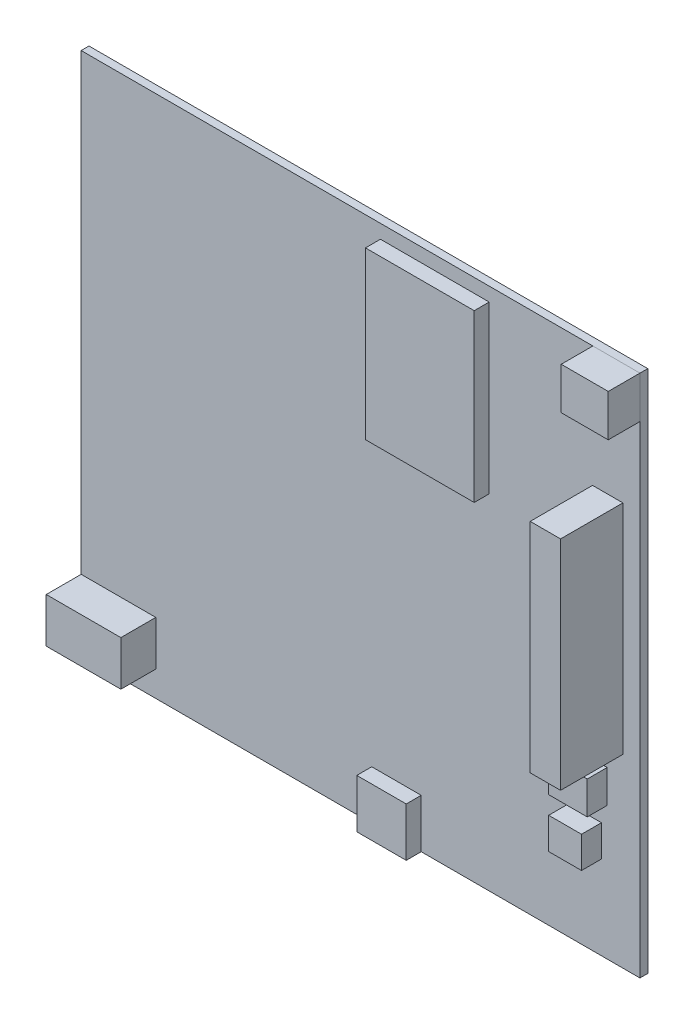
SolidWorks part; units mm, degrees
other "Foot3"
other "Foot2"
other "Foot1"
other "XBee"
other "ResetButton"
other "CommissionButton"
other "GPIO pins"
other "Barrel Jack"
other "mini-usb"
other "SMA connector"
other "base of Board"
other "Foot4"
ref_plane "Front Plane" through (0, 0, 0) normal (0, 0, 1) x (1, 0, 0)
ref_plane "Top Plane" through (0, 0, 0) normal (0, 1, 0) x (1, 0, 0)
ref_plane "Right Plane" through (0, 0, 0) normal (1, 0, 0) x (0, 0, -1)
sketch "Sketch1" plane through (0, 0, 0) normal (0, 0, 1) x (1, 0, 0)
  line L5 (0, 0) -> (112, 0)
  line L6 (0, 0) -> (0, 105)
  line L7 (0, 105) -> (112, 105)
  line L8 (112, 0) -> (112, 105)
  line L9 (59.9873, 68.9382) -> (81.7856, 68.9382)
  line L10 (59.9873, 68.9382) -> (59.9873, 102.2345)
  line L11 (59.9873, 102.2345) -> (81.7856, 102.2345)
  line L12 (81.7856, 68.9382) -> (81.7856, 102.2345)
  line L13 (14.9582, 14.0734) -> (0, 14.0734)
  line L14 (14.9582, 14.0734) -> (14.9582, 5.105)
  line L15 (14.9582, 5.105) -> (0, 5.105)
  line L16 (0, 14.0734) -> (0, 5.105)
  line L17 (97.7092, 33.2654) -> (105.4393, 33.2654)
  line L18 (97.7092, 33.2654) -> (97.7092, 26.6805)
  line L19 (97.7092, 26.6805) -> (105.4393, 26.6805)
  line L20 (105.4393, 33.2654) -> (105.4393, 26.6805)
  line L21 (97.7092, 23.1017) -> (104.2941, 23.1017)
  line L22 (97.7092, 23.1017) -> (97.7092, 16.8031)
  line L23 (97.7092, 16.8031) -> (104.2941, 16.8031)
  line L24 (104.2941, 23.1017) -> (104.2941, 16.8031)
  line L25 (94.5599, 34.4106) -> (108.5886, 34.4106)
  line L26 (94.5599, 34.4106) -> (94.5599, 14.0734)
  line L27 (94.5599, 14.0734) -> (108.5886, 14.0734)
  line L28 (108.5886, 34.4106) -> (108.5886, 14.0734)
  line L29 (58.247, 9.7929) -> (68.1586, 9.7929)
  line L30 (58.247, 9.7929) -> (58.247, 0)
  line L31 (58.247, 0) -> (68.1586, 0)
  line L32 (68.1586, 9.7929) -> (68.1586, 0)
  line L33 (108.5886, 80.7675) -> (102.5068, 80.7675)
  line L34 (108.5886, 80.7675) -> (108.5886, 37.1166)
  line L35 (108.5886, 37.1166) -> (102.5068, 37.1166)
  line L36 (102.5068, 80.7675) -> (102.5068, 37.1166)
  line L37 (102.5742, 96.5922) -> (112, 96.5922)
  line L38 (102.5742, 96.5922) -> (102.5742, 105)
  line L39 (102.5742, 105) -> (112, 105)
  line L40 (112, 96.5922) -> (112, 105)
  point P0 (0, 0)
  dimension "D1" = 105
  dimension "D2" = 112
extrude "Base PCB" add sketch "Sketch1" along normal blind 1.57 contours L37 L38 L7 L6 L13 L14 L15 L5 L30 L29 L32 L8 L36 L33 L34 L35 L12 L9 L10 L11 L25 L28 L27 L26 | L6 L5 L8 L7 region at (52.5383, 51.4076, 0)
extrude "SMA Connector" add sketch "Sketch1<3>" along normal blind 6.35 from surface separate body contours L39 L38 L37 L40 starting at face at (56, 52.5, 1.57)
sketch "Sketch1<3>" plane through (0, 0, 0) normal (0, 0, 1) x (1, 0, 0) same geometry as "Sketch1"
extrude "Mini USB" add sketch "Sketch1<4>" along normal blind 3 from surface separate body contours L29 L32 L31 L30 starting at face at (56, 52.5, 1.57)
sketch "Sketch1<4>" plane through (0, 0, 0) normal (0, 0, 1) x (1, 0, 0) same geometry as "Sketch1"
extrude "Barrel Jack" add sketch "Sketch1<5>" along normal blind 7 from surface separate body contours L13 L16 L15 L14 starting at face at (56, 52.5, 1.57)
sketch "Sketch1<5>" plane through (0, 0, 0) normal (0, 0, 1) x (1, 0, 0) same geometry as "Sketch1"
extrude "GPIO" add sketch "Sketch1<6>" along normal blind 12.5 from surface separate body contours L33 L36 L35 L34 starting at face at (56, 52.5, 1.57)
sketch "Sketch1<6>" plane through (0, 0, 0) normal (0, 0, 1) x (1, 0, 0) same geometry as "Sketch1"
extrude "Buttons" add sketch "Sketch1<7>" along normal blind 4 from surface separate body contours L20 L19 L18 L17 | L24 L23 L22 L21 starting at face at (56, 52.5, 1.57)
sketch "Sketch1<7>" plane through (0, 0, 0) normal (0, 0, 1) x (1, 0, 0) same geometry as "Sketch1"
extrude "Xbee" add sketch "Sketch1<8>" along normal blind 3 from surface separate body contours L9 L12 L11 L10 starting at face at (56, 52.5, 1.57)
sketch "Sketch1<8>" plane through (0, 0, 0) normal (0, 0, 1) x (1, 0, 0) same geometry as "Sketch1"
sketch "Sketch2" plane through (0, 0, 0) normal (0, 0, -1) x (-1, 0, 0)
  line L0 (0, 0) -> (-112, 0) construction
  line L1 (-99.3, 92.3) -> (-12.7, 92.3) construction
  line L2 (-99.3, 92.3) -> (-99.3, 12.3475) construction
  line L3 (-99.3, 12.3475) -> (-12.7, 12.3475) construction
  line L4 (-12.7, 92.3) -> (-12.7, 12.3475) construction
  line L5 (0, 105) -> (-112, 105) construction
  line L6 (0, 0) -> (0, 105) construction
  line L7 (-112, 0) -> (-112, 105) construction
  circle A0 centre (-99.3, 92.3) radius 5
  circle A1 centre (-12.7, 92.3) radius 5
  circle A2 centre (-99.3, 12.3475) radius 5
  circle A3 centre (-12.7, 12.3475) radius 5
  dimension "D1" = 10
  dimension "D2" = 12.3475
  dimension "D3" = 12.7
  dimension "D4" = 12.7
  dimension "D5" = 12.7
extrude "Boss-Extrude8" add sketch "Sketch2" along normal blind 3 from surface separate body starting at face at (56, 52.5, 0)
fillet "Fillet1" radius 3 1 edges at (104.3, 92.3, -3) second distance 1 first distance on face at (104.3, 92.3, -3)
fillet "Fillet2" radius 3 1 edges at (104.3, 12.3475, -3) second distance 1 first distance on face at (104.3, 12.3475, -3)
fillet "Fillet3" radius 3 1 edges at (17.7, 92.3, -3) second distance 1 first distance on face at (17.7, 92.3, -3)
fillet "Fillet4" radius 3 1 edges at (17.7, 12.3475, -3) second distance 1 first distance on face at (17.7, 12.3475, -3)
